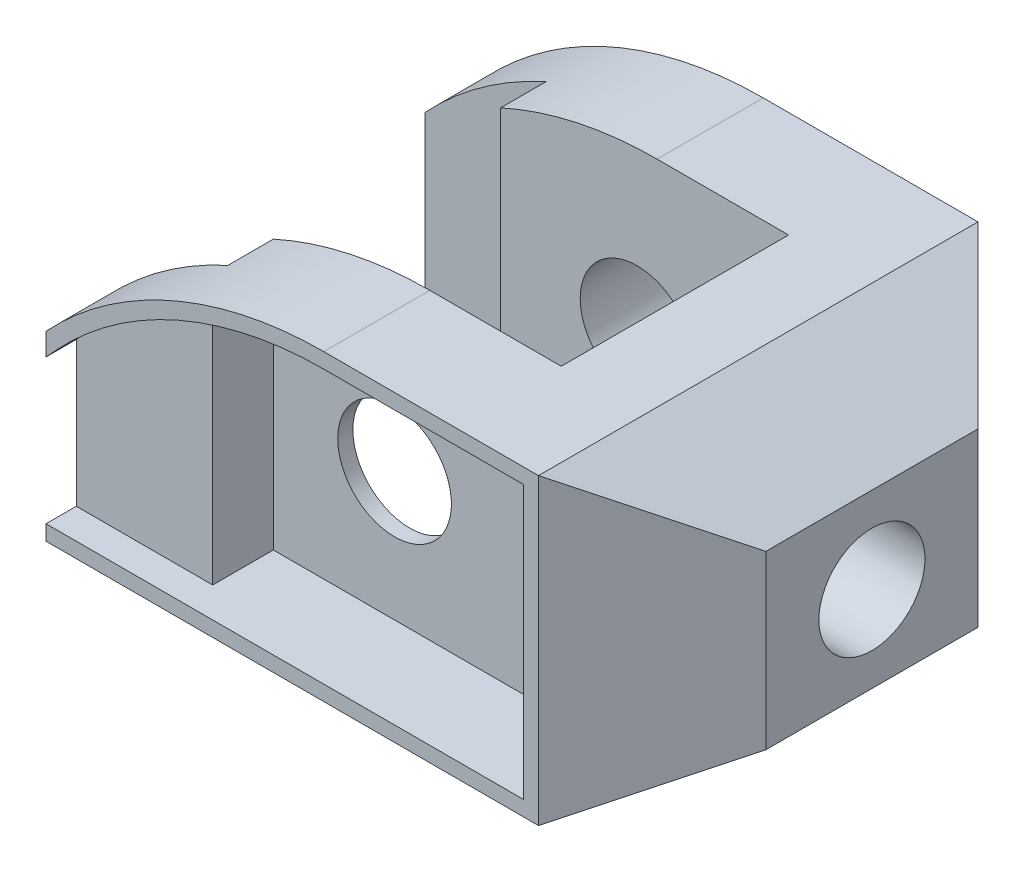
SolidWorks part; units mm, degrees
material "1060 Alloy"
ref_plane "Front Plane" through (0, 0, 0) normal (0, 0, 1) x (1, 0, 0)
ref_plane "Top Plane" through (0, 0, 0) normal (0, 1, 0) x (1, 0, 0)
ref_plane "Right Plane" through (0, 0, 0) normal (1, 0, 0) x (0, 0, -1)
sketch "Sketch1" plane through (0, 0, 0) normal (0, 0, 1) x (1, 0, 0)
  line L0 (0, 0) -> (65, 0)
  line L1 (0, 0) -> (0, 24)
  line L2 (65, 0) -> (80, 8.6603)
  line L3 (80, 8.6603) -> (80, 31.3397)
  line L4 (80, 31.3397) -> (65, 40)
  line L5 (65, 40) -> (36.6606, 40)
  arc A0 (36.6606, 40) -> (0, 24) centre (36.6606, -10) ccw
  circle A1 centre (34, 19) radius 7.5
  point P13 (36.3925, 11.6829)
  dimension "D7" = 24
  dimension "D8" = 15
  dimension "D9" = 50
  dimension "D1" = 65
  dimension "D2" = 40
  dimension "D3" = 30
  dimension "D4" = 30
  dimension "D5" = 15
  dimension "D6" = 15
  dimension "D10" = 31
  dimension "D11" = 19
extrude "Boss-Extrude1" add sketch "Sketch1" along normal mid plane 58
sketch "Sketch2" plane through (0, 0, 0) normal (0, 1, 0) x (1, 0, 0)
  line L0 (0, -29) -> (0, 29) construction
  line L1 (0, 20.9956) -> (16, 20.9956)
  line L2 (0, 20.9956) -> (0, -21)
  line L3 (0, -21) -> (16, -21)
  line L4 (16, 20.9956) -> (16, 15)
  line L5 (36.6606, 29) -> (0, 29) construction
  line L6 (0, -29) -> (36.6606, -29) construction
  line L7 (36.6606, -29) -> (36.6606, 29) construction
  line L8 (16, 15) -> (54, 15)
  line L10 (16, -15) -> (54, -15)
  line L11 (54, 15) -> (54, -15)
  line L12 (16, -15) -> (16, -21)
  line L14 (65, -29) -> (65, 29) construction
  point P10 (36.6606, 0)
  dimension "D1" = 8.0044
  dimension "D2" = 8
  dimension "D3" = 16
  dimension "D4" = 11
  dimension "D5" = 30
  dimension "D6" = 5.9956
extrude "Cut-Extrude1" cut sketch "Sketch2" along normal blind 65
sketch "Sketch4" plane through (80, 0, 0) normal (1, 0, 0) x (0, 0, -1)
  line L0 (-29, 8.6603) -> (-29, 31.3397) construction
  line L1 (-29, 0) -> (29, 0) construction
  circle A0 centre (0, 20) radius 7
  dimension "D1" = 14
  dimension "D2" = 29
  dimension "D3" = 20
extrude "Cut-Extrude2" cut sketch "Sketch4" against normal blind 38 and the other way through all
sketch "Sketch6" plane through (0, 0, 0) normal (0, 1, 0) x (1, 0, 0)
  line L0 (65, 29) -> (80, 29)
  line L1 (80, 29) -> (80, 14)
  line L2 (80, -29) -> (80, 29) construction
  line L3 (80, 14) -> (65, 29)
  line L4 (65, 29) -> (36.6606, 29) construction
  line L5 (65, -29) -> (80, -29)
  line L6 (80, -29) -> (80, -14)
  line L7 (80, -14) -> (65, -29)
  line L8 (65, -29) -> (36.6606, -29) construction
  dimension "D1" = 45
  dimension "D2" = 45
extrude "Cut-Extrude3" cut sketch "Sketch6" along normal blind 40
sketch "Sketch10" plane through (0, 0, 29) normal (0, 0, 1) x (1, 0, 0)
  line L0 (0, 2) -> (63, 2)
  line L1 (63, 2) -> (63, 38)
  line L2 (63, 38) -> (36.6606, 38)
  line L3 (1.4664, 22.64) -> (0, 21.0588)
  line L4 (0, 0) -> (65, 0)
  line L5 (65, 0) -> (65, 40)
  line L6 (65, 40) -> (36.6606, 40)
  line L7 (0, 24) -> (0, 0)
  line L8 (0, 0) -> (65, 0)
  line L9 (65, 0) -> (65, 40)
  line L10 (65, 40) -> (36.6606, 40)
  line L11 (0, 24) -> (0, 0)
  line L12 (18, 34.2242) -> (18, 2)
  line L13 (16, 35.5317) -> (16, 0) construction
  line L14 (16, 35.5317) -> (16, 0) construction
  arc A0 (36.6606, 38) -> (1.4664, 22.64) centre (36.6606, -10) ccw
  arc A1 (36.6606, 40) -> (0, 24) centre (36.6606, -10) ccw
  arc A2 (36.6606, 40) -> (0, 24) centre (36.6606, -10) ccw
  circle M8 centre (34, 19) radius 7.5
  line M13 (0, 24) -> (0, 0)
  dimension "D3" = 2
  dimension "D1" = 0
  dimension "D2" = 2
extrude "Cut-Extrude6" cut sketch "Sketch10" against normal blind 12 contours L2 A0 L12 L0 L1 M8 region at (41.5996, 19.8499, 29)
extrude "Cut-Extrude7" cut sketch "Sketch10<5>" against normal blind 4 contours L14 A0 L3 L0 M13 | A0 L14 L0 L12 region at (17.0047, 17.8932, 29) region at (8.6215, 15.2713, 29)
sketch "Sketch10<5>" plane through (0, 0, 29) normal (0, 0, 1) x (1, 0, 0) same geometry as "Sketch10"
equation "\"a\"= 58mm"
equation "\"b\"= 40mm"
equation "\"c\"= 65mm"
